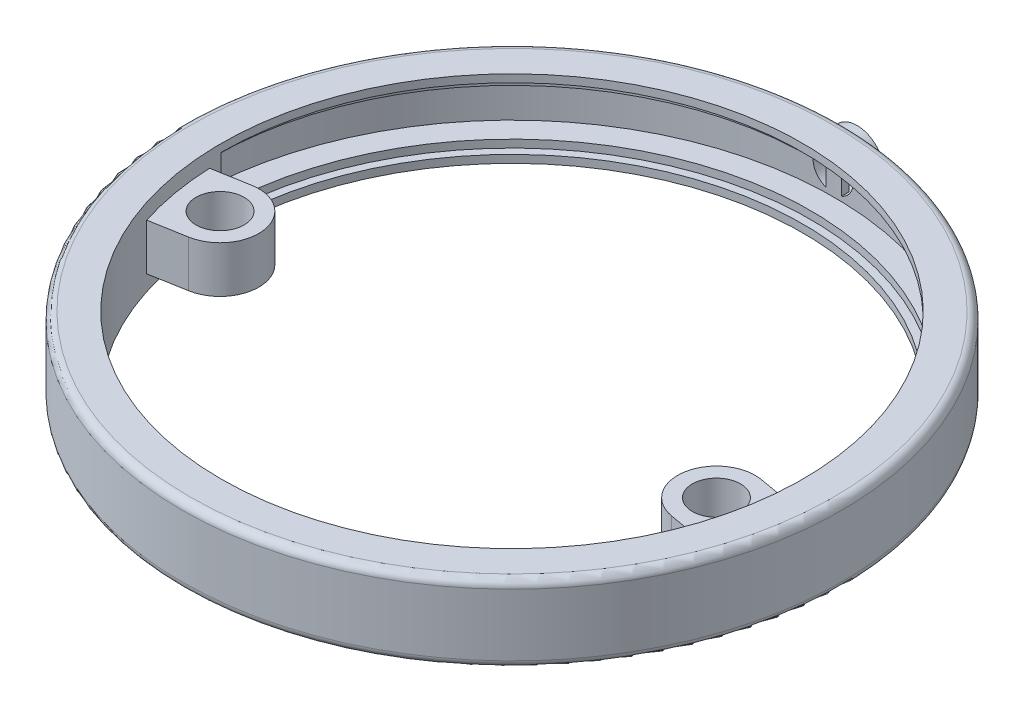
SolidWorks part; units mm, degrees
ref_plane "Front" through (0, 0, 0) normal (0, 0, 1) x (1, 0, 0)
ref_plane "Top" through (0, 0, 0) normal (0, 1, 0) x (1, 0, 0)
ref_plane "Right" through (0, 0, 0) normal (1, 0, 0) x (0, 0, -1)
sketch "草图1" plane through (0, 0, 0) normal (0, 0, 1) x (1, 0, 0)
  line L0 (3, 6) -> (3, 7)
  line L1 (0, 0) -> (3, 0)
  line L2 (0, 0) -> (0, 6)
  line L3 (0, 6) -> (3, 6)
  line L4 (3, 0) -> (3, 6) construction
  line L5 (3, 7) -> (4, 7)
  line L6 (4, 7) -> (4, 8)
  line L7 (3, 0) -> (3, -1)
  line L8 (3, -1) -> (4, -1)
  line L9 (4, -1) -> (4, -2)
  line L10 (4, 8) -> (1.5, 8)
  line L11 (4, -2) -> (1.5, -2)
  line L12 (1.5, 3) -> (41.5, 3) construction
  line L13 (41.5, 14.1916) -> (41.5, -8.1916) construction
  line L14 (1.5, 8) -> (0, 8)
  line L15 (1.5, -2) -> (0, -2)
  line L16 (-1, -1) -> (-1, 7)
  arc A0 (0, -2) -> (-1, -1) centre (0, -1) cw
  arc A1 (0, 8) -> (-1, 7) centre (0, 7) ccw
  point P12 (1.5, 6)
  point P15 (1.5, 0)
  point P17 (3, 3)
  point P19 (41.5, 3)
  point P27 (-1, 8)
  dimension "D10" = 1
  dimension "D1" = 6
  dimension "D2" = 3
  dimension "D3" = 1
  dimension "D4" = 1
  dimension "D5" = 1
  dimension "D6" = 1
  dimension "D7" = 1
  dimension "D8" = 40
  dimension "D9" = 2.5
revolve "旋转1" add sketch "草图1" angle 180 about L13
sketch "草图2" plane through (0, 0, 0) normal (0, 0, 1) x (1, 0, 0)
  line L0 (0, -2) -> (4, -2) construction
  line L1 (-1, 7) -> (-1, -1) construction
  line L2 (4, 8) -> (0, 8) construction
  line L3 (0, -2) -> (4, -2)
  line L4 (-1, 7) -> (-1, -1)
  line L5 (4, 8) -> (0, 8)
  line L6 (4, 8) -> (4, -2)
  arc A0 (-1, -1) -> (0, -2) centre (0, -1) ccw construction
  arc A1 (0, 8) -> (-1, 7) centre (0, 7) ccw construction
  arc A2 (-1, -1) -> (0, -2) centre (0, -1) ccw
  arc A3 (0, 8) -> (-1, 7) centre (0, 7) ccw
revolve "旋转2" add sketch "草图2" angle 180 about L13 reverse direction yes
ref_axis "基准轴1" through (41.5, 14.1916, 0) along (0, -1, 0)
ref_plane "基准面1" through (0, 3, 0) normal (0, -1, 0) x (-1, 0, 0)
sketch "草图4" plane through (0, 3, 0) normal (0, -1, 0) x (-1, 0, 0)
  line L0 (0, 0) -> (-83, 0) construction
  line L1 (-41.5, 0) -> (-0.6305, -7.2064) construction
  line L2 (-41.5, 0) -> (-82.3695, -7.2064) construction
  line L3 (-3.7015, -1.5878) -> (-5.438, -11.4358)
  line L4 (-3.7015, -1.5878) -> (-8.6255, -0.7195)
  line L5 (-5.438, -11.4358) -> (-10.362, -10.5676)
  line L6 (-77.562, -11.4358) -> (-79.2985, -1.5878)
  line L7 (-77.562, -11.4358) -> (-72.638, -10.5676)
  line L8 (-79.2985, -1.5878) -> (-74.3745, -0.7195)
  line L9 (-41.5, 0) -> (-41.5, -37.5) construction
  line L11 (-46.5, -39.5) -> (-36.5, -39.5)
  line L12 (-41.5, 0) -> (-9.4937, -5.6436) construction
  line L13 (-41.5, 0) -> (-73.5063, -5.6436) construction
  line L14 (-46.5, -39.5) -> (-46.5, -35.5)
  line L15 (-46.5, -35.5) -> (-36.5, -35.5)
  line L16 (-36.5, -39.5) -> (-36.5, -35.5)
  line L17 (-46.5, -39.5) -> (-36.5, -35.5) construction
  line L18 (-46.5, -35.5) -> (-36.5, -39.5) construction
  circle A0 centre (-41.5, 0) radius 41.5 construction
  circle A1 centre (-41.5, 0) radius 37.5 construction
  circle A2 centre (-9.4937, -5.6436) radius 3.1
  arc A3 (-8.6255, -0.7195) -> (-10.362, -10.5676) centre (-9.4937, -5.6436) ccw
  circle A4 centre (-73.5063, -5.6436) radius 3.1
  arc A5 (-72.638, -10.5676) -> (-74.3745, -0.7195) centre (-73.5063, -5.6436) ccw
  point P13 (-4.5697, -6.5118)
  point P17 (-4.5697, -6.5118)
  point P22 (-78.4303, -6.5118)
  point P26 (-78.4303, -6.5118)
  dimension "D7" = 75
  dimension "D8" = 5
  dimension "D9" = 2
  dimension "D10" = 160
  dimension "D11" = 10
  dimension "D1" = 5
  dimension "D2" = 10
  dimension "D5" = 6.2
  dimension "D3" = 10
  dimension "D4" = 10
  dimension "D6" = 10
  dimension "D12" = 4
extrude "凸台-拉伸5" add sketch "草图4" along normal blind 3 and the other way blind 3
sketch "草图5" plane through (0, 0, 0) normal (0, 0, 1) x (1, 0, 0)
  line L0 (-1, 3) -> (40.5, 3) construction
  line L1 (-1, 7) -> (-1, -1) construction
  line L2 (84, -1) -> (84, 7) construction
  line L3 (41.5, 3) -> (84, 3) construction
  line L5 (40.5, 5.4) -> (40.5, 0.6)
  line L7 (42.5, 5.4) -> (42.5, 0.6)
  arc A0 (42.5, 0.6) -> (42.5, 5.4) centre (41.5, 3) ccw
  arc A1 (40.5, 5.4) -> (40.5, 0.6) centre (41.5, 3) ccw
extrude "切除-拉伸1" cut sketch "草图5" against normal through all
ref_plane "基准面2" through (0, 0, -42.5) normal (0, 0, 1) x (1, 0, 0)
sketch "草图6" plane through (0, 0, -42.5) normal (0, 0, 1) x (1, 0, 0)
  circle A0 centre (41.5, 3) radius 2.6
  circle A1 centre (41.5, 3) radius 3.5
extrude "凸台-拉伸6" add sketch "草图6" against normal blind 2 and the other way blind 1
